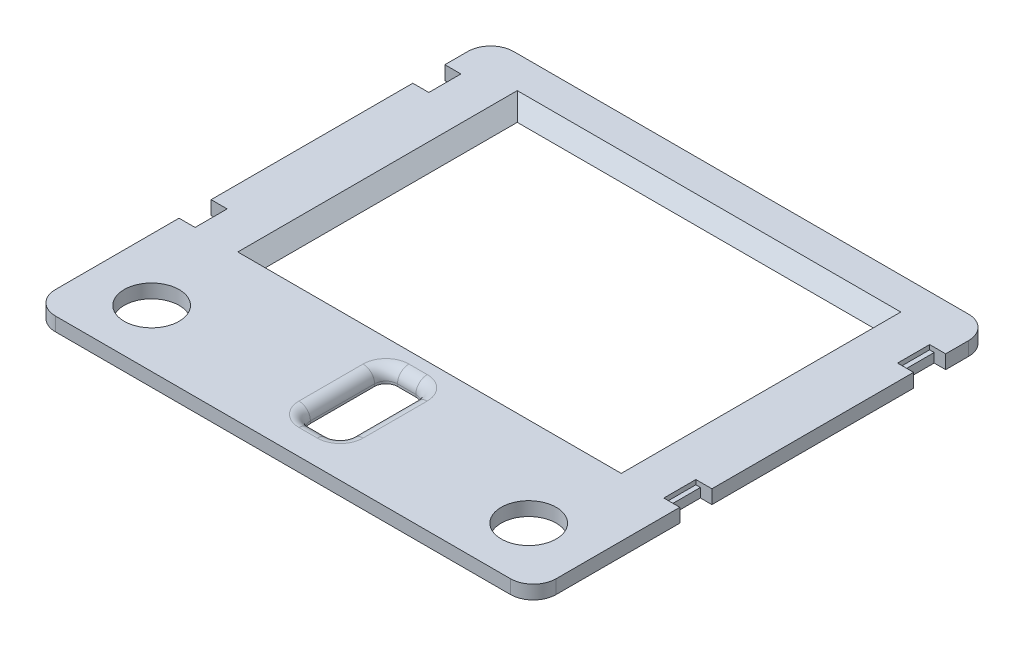
SolidWorks part; units mm, degrees
ref_plane "Front Plane" through (0, 0, 0) normal (0, 0, 1) x (1, 0, 0)
ref_plane "Top Plane" through (0, 0, 0) normal (0, 1, 0) x (1, 0, 0)
ref_plane "Right Plane" through (0, 0, 0) normal (1, 0, 0) x (0, 0, -1)
sketch "Ecran" plane through (0, 0, 0) normal (0, 1, 0) x (1, 0, 0)
  line L0 (0, -55) -> (0, 55) construction
  line L1 (-38.85, 0) -> (38.85, 0)
  line L2 (-38.85, 0) -> (-38.85, -55)
  line L3 (-38.85, -55) -> (38.85, -55)
  line L4 (38.85, 0) -> (38.85, -55)
  line L5 (0, 0) -> (0, 38.1401) construction
  line L7 (-54.65, 10) -> (54.65, 10)
  line L8 (-54.65, 10) -> (-54.65, -90)
  line L9 (-54.65, -90) -> (54.65, -90)
  line L10 (54.65, 10) -> (54.65, -90)
  line L11 (-4.5, -63) -> (4.5, -63)
  line L12 (-4.5, -63) -> (-4.5, -82)
  line L13 (-4.5, -82) -> (4.5, -82)
  line L14 (4.5, -63) -> (4.5, -82)
  line L15 (-67.0727, 6) -> (-117.0727, 6) construction
  line L16 (-67.0727, 6) -> (-67.0727, -86) construction
  line L17 (-67.0727, -86) -> (-117.0727, -86) construction
  line L18 (-117.0727, 6) -> (-117.0727, -86) construction
  line L19 (-50, -138.4781) -> (50, -138.4781) construction
  line L20 (-50, -138.4781) -> (-50, -234.5028) construction
  line L21 (-50, -234.5028) -> (50, -234.5028) construction
  line L22 (50, -138.4781) -> (50, -234.5028) construction
  line L27 (-3, -134.5393) -> (-3, -144.1699) construction
  line L29 (-3, -137.0759) -> (-3, -141.3957) construction
  line L31 (-7, -137.0759) -> (-7, -141.3957) construction
  line L33 (0, -134.5393) -> (9.6306, -134.5393) construction
  line L36 (-37.0528, -138.4781) -> (-42.8528, -138.4781) construction
  line L37 (-38.85, 0) -> (-100.731, 0) construction
  line L38 (-38.85, 0) -> (-38.85, -11.01) construction
  line L39 (-38.85, -11.01) -> (-100.731, -11.01) construction
  line L40 (-100.731, 0) -> (-100.731, -11.01) construction
  line L41 (-38.85, -55) -> (-99.7775, -55) construction
  line L42 (-38.85, -55) -> (-38.85, -43.99) construction
  line L43 (-38.85, -43.99) -> (-99.7775, -43.99) construction
  line L44 (-99.7775, -55) -> (-99.7775, -43.99) construction
  circle A6 centre (-41.15, -77.5) radius 6
  circle A7 centre (41.15, -77.5) radius 6
  point P6 (0, 0)
  point P30 (0, -63)
  point P43 (-4.5, -72.5)
  dimension "D5" = 50
  dimension "D9" = 4
  dimension "D13" = 19
  dimension "D16" = 12
  dimension "D1" = 55
  dimension "D2" = 77.7
  dimension "D3" = 109.3
  dimension "D4" = 92
  dimension "D6" = 10
  dimension "D7" = 15.8
  dimension "D8" = 15.8
  dimension "D10" = 13.5
  dimension "D11" = 12.5
  dimension "D12" = 35
  dimension "D14" = 8
  dimension "D15" = 9
  dimension "D17" = 100
  dimension "D18" = 8.5
  dimension "D19" = 100
  dimension "D20" = 4.65
  dimension "D21" = 8.85
  dimension "D22" = 4
  dimension "D23" = 8.85
  dimension "D24" = 3
  dimension "D25" = 4
  dimension "D26" = 7
  dimension "D27" = 13.5
  dimension "D28" = 4.65
  dimension "D29" = 11.15
  dimension "D30" = 11.01
  dimension "D31" = 11.01
  dimension "D32" = 6
  dimension "D33" = 31
  dimension "D34" = 17.01
  dimension "D35" = 42.01
  dimension "D36" = 32.98
  dimension "D38" = 109.3
extrude "Boss-Extrude1" add sketch "Ecran" along normal blind 3
chamfer "Chamfer1" distance 3 angle 45 4 edges at (0, 3, 55) (38.85, 3, 27.5) (-38.85, 3, 27.5) (0, 3, 0)
fillet "Fillet1" radius 5 4 edges at (54.65, 1.5, 90) (-54.65, 1.5, 90) (-54.65, 1.5, -10) (54.65, 1.5, -10)
sketch "Sketch2" plane through (0, 3, 0) normal (0, 1, 0) x (1, 0, 0)
  line L0 (54.65, -51.02) -> (52.15, -51.02)
  line L1 (-54.65, 5) -> (-54.65, -85) construction
  line L2 (-54.65, 0) -> (-52.15, 0)
  line L3 (-54.65, 0) -> (-54.65, -7)
  line L4 (-54.65, -7) -> (-52.15, -7)
  line L5 (-52.15, 0) -> (-52.15, -7)
  line L6 (49.65, 10) -> (-49.65, 10) construction
  line L7 (0, -55) -> (0, 55) construction
  line L8 (52.15, 0) -> (52.15, -7)
  line L9 (54.65, 0) -> (52.15, 0)
  line L10 (54.65, 0) -> (54.65, -7)
  line L11 (54.65, -7) -> (52.15, -7)
  line L12 (-70.6295, -29.01) -> (90.8476, -29.01) construction
  line L13 (54.65, -58.02) -> (54.65, -51.02)
  line L14 (54.65, -58.02) -> (52.15, -58.02)
  line L15 (52.15, -58.02) -> (52.15, -51.02)
  line L16 (-52.15, -58.02) -> (-52.15, -51.02)
  line L17 (-54.65, -58.02) -> (-54.65, -51.02)
  line L18 (-54.65, -58.02) -> (-52.15, -58.02)
  line L19 (-54.65, -51.02) -> (-52.15, -51.02)
  dimension "D1" = 10
  dimension "D2" = 7
  dimension "D3" = 2.5
  dimension "D4" = 39.01
extrude "Cut-Extrude1" cut sketch "Sketch2" against normal through all
sketch "Sketch3" plane through (0, 3, 0) normal (0, 1, 0) x (1, 0, 0)
  line L1 (-52.15, 0) -> (-51.15, 0)
  line L2 (-52.15, 0) -> (-52.15, -7)
  line L3 (-52.15, -7) -> (-51.15, -7)
  line L4 (-51.15, 0) -> (-51.15, -7)
  line L5 (49.65, 10) -> (-49.65, 10) construction
  line L6 (-54.65, 5) -> (-54.65, 0) construction
  line L7 (-73.4244, -29.01) -> (96.2537, -29.01) construction
  line L8 (-51.15, -58.02) -> (-51.15, -51.02)
  line L9 (-52.15, -51.02) -> (-51.15, -51.02)
  line L10 (-52.15, -58.02) -> (-52.15, -51.02)
  line L11 (-52.15, -58.02) -> (-51.15, -58.02)
  line L12 (0, -55) -> (0, 55) construction
  line L13 (52.15, -58.02) -> (51.15, -58.02)
  line L14 (52.15, -58.02) -> (52.15, -51.02)
  line L15 (52.15, -51.02) -> (51.15, -51.02)
  line L16 (51.15, -58.02) -> (51.15, -51.02)
  line L17 (51.15, 0) -> (51.15, -7)
  line L18 (52.15, -7) -> (51.15, -7)
  line L19 (52.15, 0) -> (52.15, -7)
  line L20 (52.15, 0) -> (51.15, 0)
  dimension "D1" = 7
  dimension "D2" = 10
  dimension "D3" = 2.5
  dimension "D4" = 1
  dimension "D5" = 39.01
extrude "Cut-Extrude2" cut sketch "Sketch3" against normal blind 1
fillet "Fillet2" radius 2.5 4 edges at (4.5, 1.5, 82) (-4.5, 1.5, 82) (4.5, 1.5, 63) (-4.5, 1.5, 63)
fillet "Fillet3" radius 2.5 8 edges at (-3.7678, 3, 63.7322) (0, 3, 63) (3.7678, 3, 63.7322) (4.5, 3, 72.5) (3.7678, 3, 81.2678) (0, 3, 82) (-3.7678, 3, 81.2678) (-4.5, 3, 72.5)
equation "\"1po\"=1"
